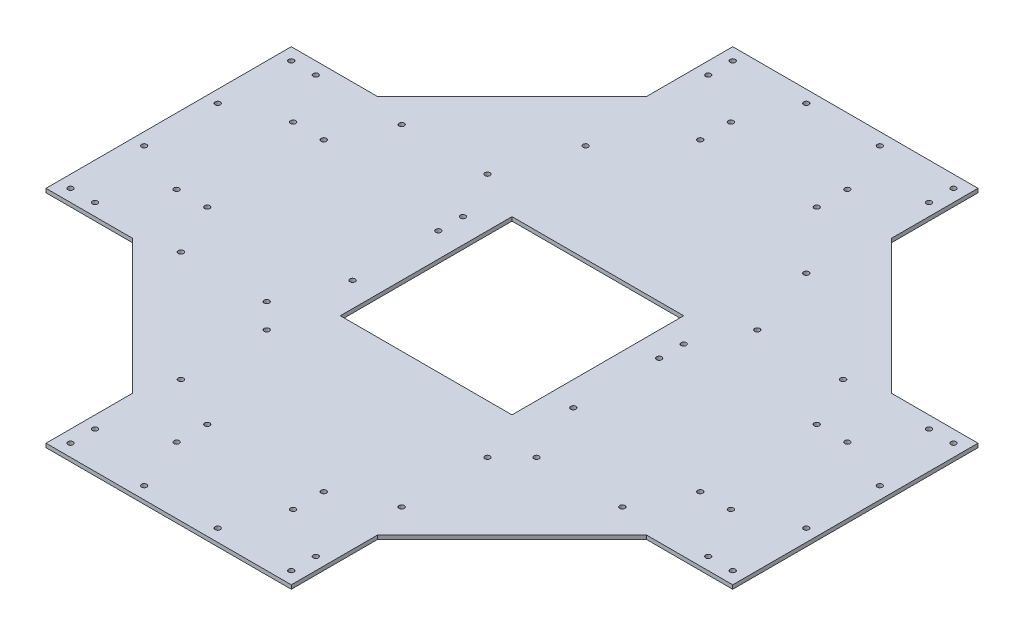
SolidWorks part; units mm, degrees
ref_plane "Front Plane" through (0, 0, 0) normal (0, 0, 1) x (1, 0, 0)
ref_plane "Top Plane" through (0, 0, 0) normal (0, 1, 0) x (1, 0, 0)
ref_plane "Right Plane" through (0, 0, 0) normal (1, 0, 0) x (0, 0, -1)
sketch "Sketch1" plane through (0, 0, 0) normal (0, 1, 0) x (1, 0, 0)
  line L0 (0, -280) -> (100, -280)
  line L1 (100, -280) -> (100, -209.6016)
  line L2 (280, -100) -> (209.6016, -100)
  line L3 (0, 0) -> (0, -280) construction
  line L4 (280, 0) -> (280, -100)
  line L5 (-280, 280) -> (280, 280) construction
  line L6 (-280, 280) -> (-280, -280) construction
  line L7 (-280, -280) -> (280, -280) construction
  line L8 (280, 280) -> (280, -280) construction
  line L9 (-280, 280) -> (280, -280) construction
  line L10 (-280, -280) -> (280, 280) construction
  line L11 (100, -209.6016) -> (209.6016, -100)
  line L12 (-280, 0) -> (-280, -100)
  line L13 (-280, -100) -> (-209.6016, -100)
  line L14 (-209.6016, -100) -> (-100, -209.6016)
  line L15 (-100, -280) -> (-100, -209.6016)
  line L16 (0, -280) -> (-100, -280)
  line L17 (0, 280) -> (-100, 280)
  line L18 (-100, 280) -> (-100, 209.6016)
  line L19 (-100, 209.6016) -> (-209.6016, 100)
  line L20 (-280, 100) -> (-209.6016, 100)
  line L21 (-280, 0) -> (-280, 100)
  line L22 (280, 0) -> (280, 100)
  line L23 (280, 100) -> (209.6016, 100)
  line L24 (209.6016, 100) -> (100, 209.6016)
  line L25 (100, 280) -> (100, 209.6016)
  line L26 (0, 280) -> (100, 280)
  line L27 (111.5258, -219.2889) -> (219.2889, -111.5258) construction
  line L28 (219.2889, -111.5258) -> (247.5732, -139.8101) construction
  line L29 (247.5732, -139.8101) -> (139.8101, -247.5732) construction
  line L30 (139.8101, -247.5732) -> (111.5258, -219.2889) construction
  line L31 (-100, -270) -> (100, -270) construction
  line L32 (-90, -280) -> (-90, 280) construction
  line L33 (-70, -70) -> (70, -70)
  line L34 (-70, -70) -> (-70, 70)
  line L35 (-70, 70) -> (70, 70)
  line L36 (70, -70) -> (70, 70)
  line L37 (-70, -70) -> (70, 70) construction
  line L38 (-70, 70) -> (70, -70) construction
  line L39 (-100, -260) -> (100, -260) construction
  line L40 (-280, 40) -> (280, 40) construction
  line L41 (0, 280) -> (0, 0) construction
  line L42 (-280, -90) -> (280, -90) construction
  line L43 (-260, -100) -> (-260, 100) construction
  line L44 (0, 0) -> (-280, 0) construction
  arc A0 (100, -280) -> (280, -100) centre (100, -100) ccw construction
  circle A1 centre (-47.5, -201) radius 2.125
  circle A2 centre (-47.5, -226) radius 2.125
  circle A3 centre (47.5, -226) radius 2.125
  circle A4 centre (47.5, -201) radius 2.125
  circle A5 centre (-201, 47.5) radius 2.125
  circle A6 centre (-226, 47.5) radius 2.125
  circle A7 centre (-201, -47.5) radius 2.125
  circle A8 centre (-226, -47.5) radius 2.125
  circle A9 centre (47.5, 201) radius 2.125
  circle A10 centre (47.5, 226) radius 2.125
  circle A11 centre (-47.5, 201) radius 2.125
  circle A12 centre (-47.5, 226) radius 2.125
  circle A13 centre (201, -47.5) radius 2.125
  circle A14 centre (226, -47.5) radius 2.125
  circle A15 centre (201, 47.5) radius 2.125
  circle A16 centre (226, 47.5) radius 2.125
  circle A17 centre (-90, -270) radius 2.125
  circle A18 centre (-30, -270) radius 2.125
  circle A19 centre (30, -270) radius 2.125
  circle A20 centre (90, -270) radius 2.125
  circle A21 centre (-270, 90) radius 2.125
  circle A22 centre (-270, 30) radius 2.125
  circle A23 centre (-270, -30) radius 2.125
  circle A24 centre (-270, -90) radius 2.125
  circle A25 centre (90, 270) radius 2.125
  circle A26 centre (30, 270) radius 2.125
  circle A27 centre (-30, 270) radius 2.125
  circle A28 centre (-90, 270) radius 2.125
  circle A29 centre (270, -90) radius 2.125
  circle A30 centre (270, -30) radius 2.125
  circle A31 centre (270, 30) radius 2.125
  circle A32 centre (270, 90) radius 2.125
  circle A33 centre (-90, -250) radius 2.125
  circle A34 centre (-90, -180) radius 2.125
  circle A35 centre (-90, -110) radius 2.125
  circle A36 centre (-90, -40) radius 2.125
  circle A37 centre (-90, 30) radius 2.125
  circle A38 centre (-90, 50) radius 2.125
  circle A39 centre (-90, 100) radius 2.125 construction
  circle A40 centre (-90, 150) radius 2.125
  circle A41 centre (-90, 200) radius 2.125 construction
  circle A42 centre (-90, 250) radius 2.125
  circle A43 centre (90, -250) radius 2.125
  circle A44 centre (90, -180) radius 2.125
  circle A45 centre (90, -110) radius 2.125
  circle A46 centre (90, -40) radius 2.125
  circle A47 centre (90, 30) radius 2.125
  circle A48 centre (90, 50) radius 2.125
  circle A49 centre (90, 100) radius 2.125 construction
  circle A50 centre (90, 150) radius 2.125
  circle A51 centre (90, 200) radius 2.125 construction
  circle A52 centre (90, 250) radius 2.125
  circle A53 centre (-250, -90) radius 2.125
  circle A54 centre (-180, -90) radius 2.125
  circle A55 centre (-110, -90) radius 2.125
  circle A56 centre (-110, 90) radius 2.125
  circle A57 centre (-180, 90) radius 2.125
  circle A58 centre (-250, 90) radius 2.125
  circle A59 centre (110, -90) radius 2.125
  circle A60 centre (180, -90) radius 2.125
  circle A61 centre (250, -90) radius 2.125
  circle A62 centre (110, 90) radius 2.125
  circle A63 centre (180, 90) radius 2.125
  circle A64 centre (250, 90) radius 2.125
  point P33 (0, 0)
  point P68 (0, 0)
  point P107 (0, 0)
  dimension "D10" = 25
  dimension "4.25" = 4.25
  dimension "D11" = 4.25
  dimension "D16" = 4.25
  dimension "D24" = 4.25
  dimension "D28" = 4.25
  dimension "D32" = 4.25
  dimension "D1" = 560
  dimension "D2" = 90
  dimension "D3" = 280
  dimension "D4" = 4
  dimension "D5" = 100
  dimension "D6" = 155
  dimension "D7" = 152.4
  dimension "D8" = 15
  dimension "D9" = 40
  dimension "D12" = 47.5
  dimension "D13" = 54
  dimension "D15" = 10
  dimension "D17" = 10
  dimension "D18" = 76.2
  dimension "D19" = 140
  dimension "D20" = 140
  dimension "D23" = 10
  dimension "D25" = 10
  dimension "D26" = 300
  dimension "D29" = 10
  dimension "D31" = 20
  dimension "D33" = 10
  dimension "D21" = 4
  dimension "D27" = 5
  dimension "D30" = 5
  dimension "D34" = 3
  dimension "D14" = 4
  dimension "D22" = 4
extrude "Boss-Extrude1" add sketch "Sketch1" along normal blind 3.175 contours L26 L17 L18 L19 L20 L21 L12 L13 L14 L15 L16 L0 L1 L11 L2 L4 L22 L23 L24 L25 region at (-50, 0, 272.0804)
